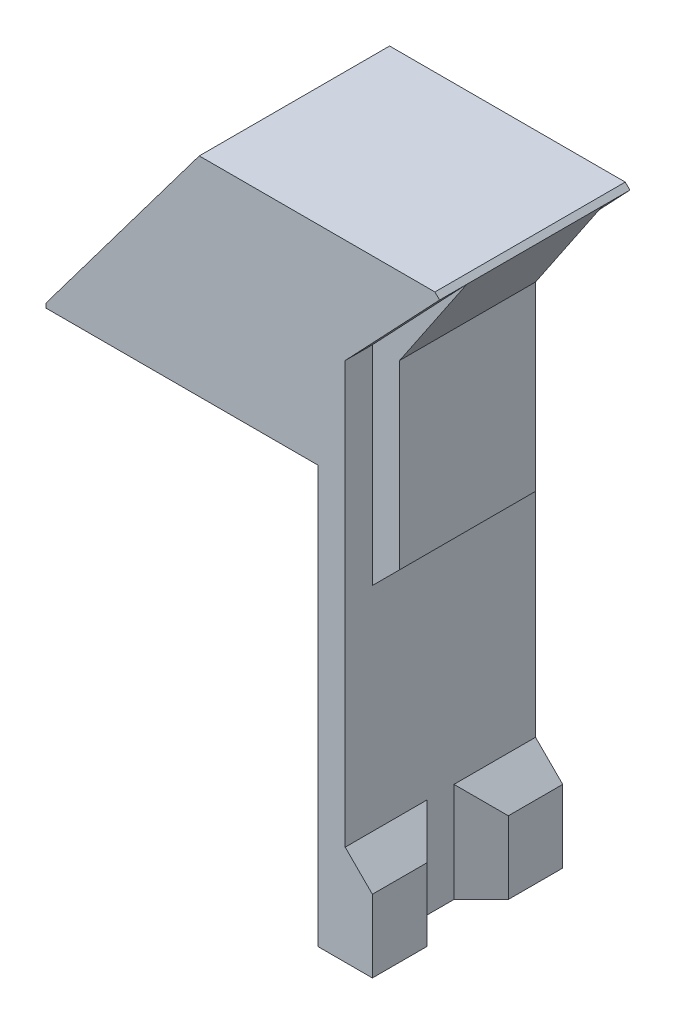
SolidWorks part; units mm, degrees
ref_plane "Front Plane" through (0, 0, 0) normal (0, 0, 1) x (1, 0, 0)
ref_plane "Top Plane" through (0, 0, 0) normal (0, 1, 0) x (1, 0, 0)
ref_plane "Right Plane" through (0, 0, 0) normal (1, 0, 0) x (0, 0, -1)
sketch "Sketch1" plane through (0, 0, 0) normal (1, 0, 0) x (0, 0, -1)
  line L0 (0, 0) -> (0, 46)
  line L1 (0, 0) -> (21, 0)
  line L2 (21, 0) -> (21, 46)
  line L3 (21, 46) -> (0, 46)
  dimension "D1" = 46
  dimension "D2" = 21
extrude "Boss-Extrude1" add sketch "Sketch1" along normal blind 3
sketch "Sketch2" plane through (3, 0, 0) normal (1, 0, 0) x (0, 0, -1)
  line L1 (0, 0) -> (6, 0)
  line L2 (0, 0) -> (0, 8)
  line L3 (0, 8) -> (6, 8)
  line L4 (6, 0) -> (6, 8)
  line L5 (21, 0) -> (15, 0)
  line L6 (21, 0) -> (21, 8)
  line L7 (21, 8) -> (15, 8)
  line L8 (15, 0) -> (15, 8)
  dimension "D1" = 6
  dimension "D2" = 8
  dimension "D3" = 6
extrude "Boss-Extrude2" add sketch "Sketch2" along normal blind 3
chamfer "Chamfer1" distance 3 angle 45 2 edges at (3, 4, -15)
sketch "Sketch3" plane through (0, 0, 0) normal (0, 0, 1) x (1, 0, 0)
  line L0 (0, 46) -> (-30, 46)
  line L1 (3, 46) -> (3, 69) construction
  line L2 (-30, 69) -> (-13.1, 69) construction
  line L3 (-30, 46) -> (-30, 46.5)
  line L4 (-30, 46.5) -> (-13.1, 69)
  line L5 (-13.1, 69) -> (13.9, 69)
  line L6 (13.9, 69) -> (3, 57.5)
  line L7 (3, 57.5) -> (3, 46)
  line L8 (0, 46) -> (3, 46)
  dimension "D1" = 30
  dimension "D2" = 23
  dimension "D3" = 16.9
  dimension "D4" = 0.5
  dimension "D5" = 27
extrude "Boss-Extrude3" add sketch "Sketch3" against normal up to surface (21 mm away) contours L4 L5 L6 L7 L8 L0 L3 up to face at (3, 18, -21)
chamfer "Chamfer2" distance 3 angle 45 2 edges at (3, 8, -16.5)
chamfer "Chamfer3" distance 1 angle 45 1 edges at (13.9, 69, -10.5) first distance on face at (0.4, 69, -10.5)
sketch "Sketch4" plane through (3, 0, 0) normal (1, 0, 0) x (0, 0, -1)
  line L0 (21, 57.5) -> (0, 57.5) construction
  line L1 (3, 57.5) -> (18, 57.5)
  line L2 (3, 57.5) -> (3, 37.5)
  line L3 (3, 37.5) -> (18, 37.5)
  line L4 (18, 57.5) -> (18, 37.5)
  line L5 (0, 57.5) -> (0, 11) construction
  line L6 (21, 11) -> (21, 57.5) construction
  dimension "D1" = 3
  dimension "D2" = 3
  dimension "D3" = 20
extrude "Boss-Extrude4" add sketch "Sketch4" along normal blind 3
sketch "Sketch5" plane through (0, 0, -3) normal (0, 0, 1) x (1, 0, 0)
  line L0 (6, 57.5) -> (13.4134, 68.4866)
  line L1 (6, 57.5) -> (3, 57.5)
  line L11 (3, 57.5) -> (13.4134, 68.4866)
  line L12 (13.4134, 68.4866) -> (12.9, 69)
  line L13 (12.9, 69) -> (-13.1, 69)
  line L14 (-13.1, 69) -> (-30, 46.5)
  line L15 (-30, 46.5) -> (-30, 46)
  line L16 (-30, 46) -> (0, 46)
  line L17 (0, 46) -> (0, 0)
  line L18 (0, 0) -> (6, 0)
  line L19 (6, 0) -> (6, 8)
  line L20 (6, 8) -> (3, 11)
  line L21 (3, 11) -> (3, 57.5)
  line L22 (3, 57.5) -> (13.4134, 68.4866)
  line L23 (13.4134, 68.4866) -> (12.9, 69)
  line L24 (12.9, 69) -> (-13.1, 69)
  line L25 (-13.1, 69) -> (-30, 46.5)
  line L26 (-30, 46.5) -> (-30, 46)
  line L27 (-30, 46) -> (0, 46)
  line L28 (0, 46) -> (0, 0)
  line L29 (0, 0) -> (6, 0)
  line L30 (6, 0) -> (6, 8)
  line L31 (6, 8) -> (3, 11)
  line L32 (3, 11) -> (3, 57.5)
  line M15 (6, 57.5) -> (3, 57.5)
  dimension "D1" = 0
extrude "Boss-Extrude5" add sketch "Sketch5" against normal up to surface (15 mm away) contours L22 L0 M15 region at (7.4711, 61.1622, -3) up to face at (4.5, 47.5, -18)
chamfer "Chamfer4" distance 3 angle 45 1 edges at (3, 37.5, -10.5)
